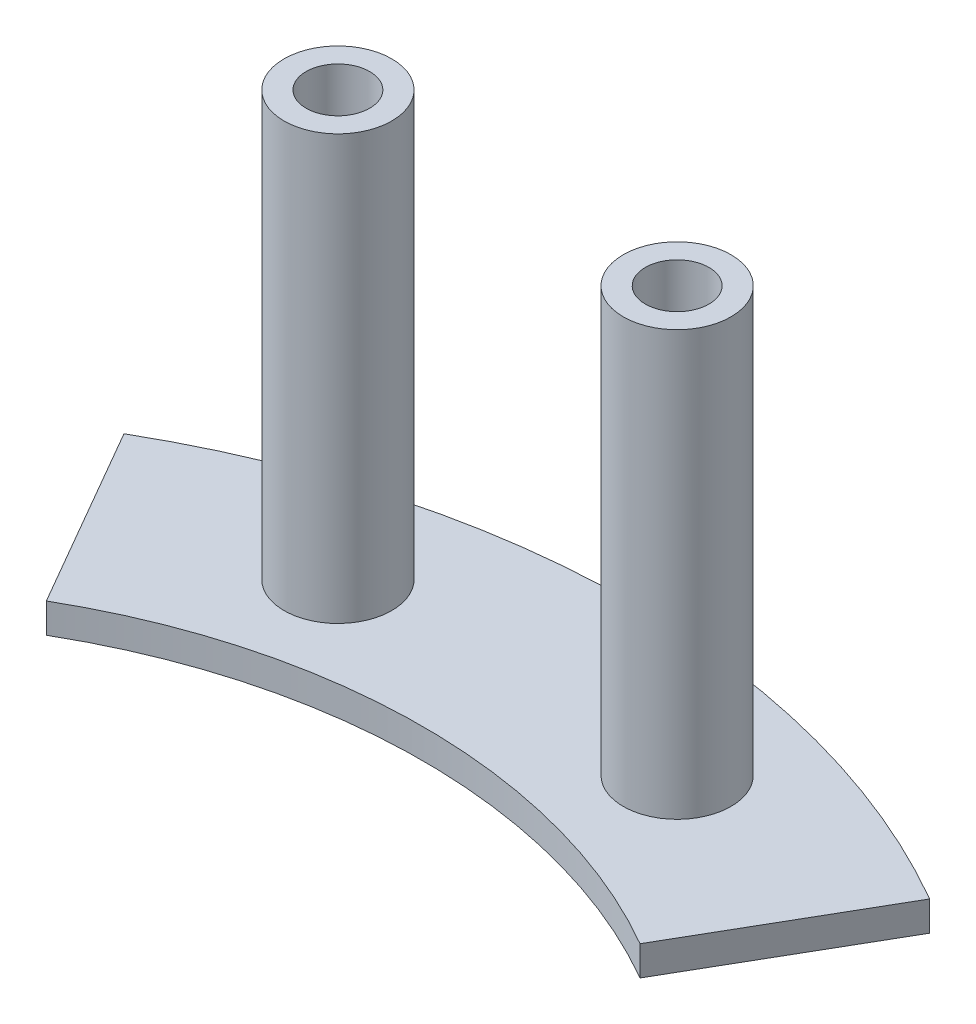
SolidWorks part; units mm, degrees
ref_plane "Front Plane" through (0, 0, 0) normal (0, 0, 1) x (1, 0, 0)
ref_plane "Top Plane" through (0, 0, 0) normal (0, 1, 0) x (1, 0, 0)
ref_plane "Right Plane" through (0, 0, 0) normal (1, 0, 0) x (0, 0, -1)
sketch "Sketch1" plane through (0, 0, 0) normal (0, 1, 0) x (1, 0, 0)
  line L0 (-14, 24.2487) -> (-19, 32.909) construction
  line L1 (14, 24.2487) -> (19, 32.909) construction
  line L2 (0, 0) -> (4, 0) construction
  line L3 (-19, 32.909) -> (-14, 24.2487)
  line L4 (19, 32.909) -> (14, 24.2487)
  circle A0 centre (0, 0) radius 28 construction
  circle A1 centre (0, 0) radius 38 construction
  arc A2 (-19, 32.909) -> (19, 32.909) centre (0, 0) cw
  arc A3 (-14, 24.2487) -> (14, 24.2487) centre (0, 0) cw
  arc A4 (-16.5, 28.5788) -> (16.5, 28.5788) centre (0, 0) cw construction
  dimension "D1" = 28
  dimension "D2" = 76
  dimension "D6" = 60
  dimension "D3" = 60
extrude "Boss-Extrude1" add sketch "Sketch1" along normal blind 1.4
sketch "Sketch2" plane through (0, 1.4, 0) normal (0, 1, 0) x (1, 0, 0)
  line L0 (-19, 32.909) -> (-14, 24.2487) construction
  line L2 (-8, 32) -> (8, 32) construction
  line L3 (0, 32) -> (0, 0) construction
  line L4 (14, 24.2487) -> (19, 32.909) construction
  arc A0 (-16.5, 28.5788) -> (16.5, 28.5788) centre (0, 0) cw construction
  circle A1 centre (-8, 32) radius 2.54
  circle A2 centre (8, 32) radius 2.54
  dimension "D1" = 5.08
  dimension "D2" = 8
  dimension "D3" = 32
extrude "Boss-Extrude2" add sketch "Sketch2" along normal blind 20
sketch "Sketch5" plane through (0, 21.4, 0) normal (0, 1, 0) x (1, 0, 0)
  circle A0 centre (-8, 32) radius 1.5
  circle A2 centre (8, 32) radius 1.5
  dimension "D1" = 3
extrude "Cut-Extrude1" cut sketch "Sketch5" against normal blind 3
